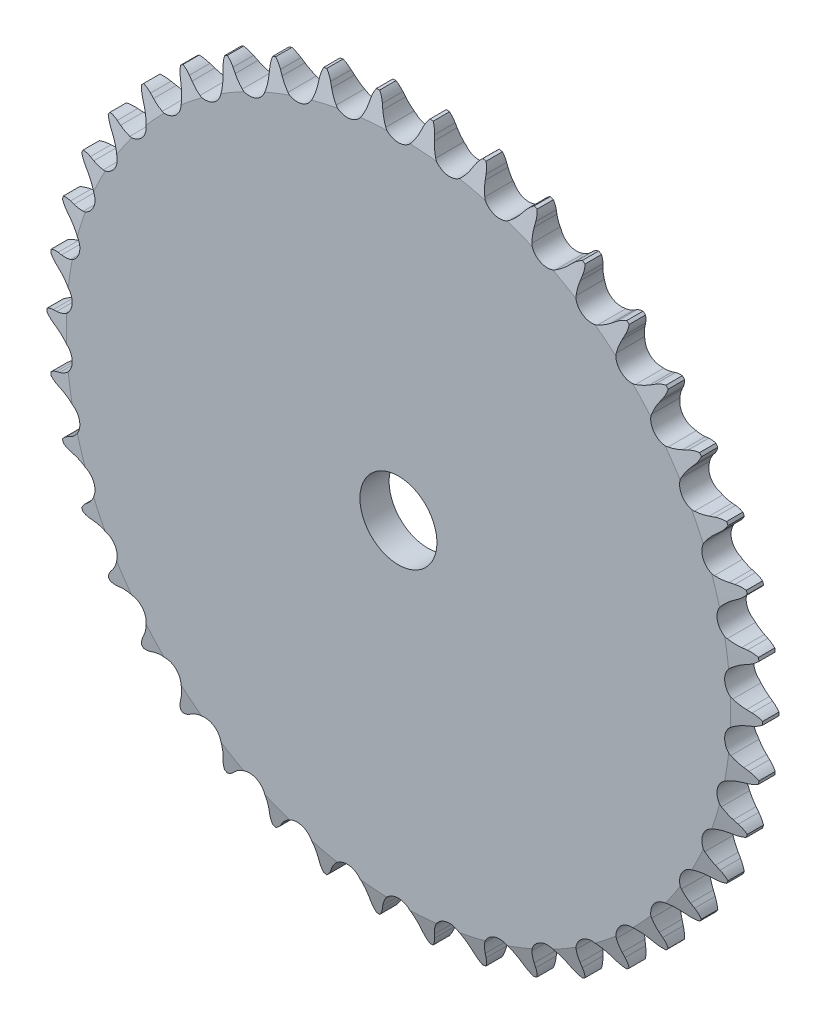
SolidWorks part; units mm, degrees
ref_plane "Front Plane" through (0, 0, 0) normal (0, 0, 1) x (1, 0, 0)
ref_plane "Top Plane" through (0, 0, 0) normal (0, 1, 0) x (1, 0, 0)
ref_plane "Right Plane" through (0, 0, 0) normal (1, 0, 0) x (0, 0, -1)
ref_axis "Axis1" through (0, 0, -88.99) along (0, 0, 1)
sketch "Sprocket-BaseSketch" plane through (0, 0, 0) normal (1, 0, 0) x (0, 0, -1)
  line L0 (3.6068, 0) -> (3.6068, 82.1949)
  line L1 (3.6068, 82.1949) -> (2.0193, 88.5449)
  line L2 (2.0193, 88.5449) -> (-2.0193, 88.5449)
  line L3 (-2.0193, 88.5449) -> (-3.6068, 82.1949)
  line L4 (-3.6068, 82.1949) -> (-3.6068, 0)
  line L5 (-3.6068, 0) -> (3.6068, 0)
  line L6 (14.4272, 0) -> (-4.5085, 0) construction
  dimension "Hub Surface" = 3.6068
  dimension "RightSide (1)" = 1.5875
  dimension "RightSide (2)" = 6.35
  dimension "OD" = 88.5449
  dimension "LeftSide (1)" = 1.5875
  dimension "LeftSide (2)" = 6.35
  dimension "Tooth Width" = 7.2136
revolve "40 (08A) ANSI (ISO) Chain Number, 6.691in P.D." add sketch "Sprocket-BaseSketch" angle 360 about L6
sketch "Tooth-Sketch" plane through (0, 0, 0) normal (0, 0, 1) x (1, 0, 0)
  line L0 (0, 0) -> (0, 113.2966) construction
  line L1 (4.649, 85.2343) -> (5.0352, 86.3092)
  line L2 (-4.649, 85.2343) -> (-5.0352, 86.3092)
  line L3 (0, 84.9725) -> (12.6645, 84.0234) construction
  line L4 (0, 84.9725) -> (-12.6645, 84.0234) construction
  arc A0 (-3.2347, 82.5851) -> (3.2347, 82.5851) centre (0, 84.9725) ccw
  arc A1 (3.2347, 82.5851) -> (4.649, 85.2343) centre (-5.101, 88.7372) ccw
  arc A2 (-3.2347, 82.5851) -> (-4.649, 85.2343) centre (5.101, 88.7372) cw
  arc A3 (5.0352, 86.3092) -> (11.0637, 90.5491) centre (11.0637, 84.1434) cw
  arc A4 (-5.0352, 86.3092) -> (-11.0637, 90.5491) centre (-11.0637, 84.1434) ccw
  arc A5 (11.0637, 90.5491) -> (-11.0637, 90.5491) centre (0, 0) ccw
extrude "Tooth-Cut, Number of teeth: 42" cut sketch "Tooth-Sketch" against normal through all and the other way through all
pattern_circular "Tooth Pattern, 42 / 42" count 42 every 8.571 about axis through (0, 0, -88.99) along (0, 0, 1) of "Tooth-Cut, Number of teeth: 42"
sketch "Sketch3" plane through (0, 0, 0) normal (1, 0, 0) x (0, 0, -1)
  line L0 (-21.3614, 0) -> (21.3614, 0) construction
  line L1 (3.6068, 0) -> (3.6068, 44.45)
  line L2 (3.6068, 44.45) -> (24.9682, 44.45)
  line L3 (24.9682, 44.45) -> (24.9682, 0)
  line L4 (24.9682, 0) -> (3.6068, 0)
  dimension "Hub Mounting" = 3.6068
  dimension "Hub OD" = 44.45
  dimension "Hub Width" = 21.3614
revolve "Hub-Revolve1" add sketch "Sketch3" angle 360 about L0
sketch "Sketch4" plane through (0, 0, -24.9682) normal (0, 0, -1) x (-1, 0, 0)
  circle A0 centre (0, 0) radius 9.525
  dimension "Bore Diameter " = 19.05
extrude "Cut-Extrude1" cut sketch "Sketch4" against normal through all
sketch "Sketch5" plane through (0, 0, 0) normal (1, 0, 0) x (0, 0, -1)
  line L0 (24.9682, 0) -> (-3.6068, 0) construction
  line L1 (24.9682, -44.45) -> (24.9682, 44.45) construction
  line L2 (-3.6068, 3.2885) -> (-3.6068, -3.2885) construction
ref_plane "Plane1" through (0, 0, 0) normal (-0.0747, 0.9972, 0) x (-0.9972, -0.0747, 0)
sketch "Sketch6" plane through (0, 0, -24.9682) normal (0, 0, -1) x (-1, 0, 0)
  line L0 (-1.6854, 9.3747) -> (-1.5074, 11.7493)
  line L1 (-1.5074, 11.7493) -> (3.2417, 11.3934)
  line L2 (3.2417, 11.3934) -> (3.0638, 9.0188)
  line L3 (3.0638, 9.0188) -> (-1.6854, 9.3747)
  line L4 (15.6723, -1.1745) -> (-15.6723, 1.1745) construction
  circle A0 centre (0, 0) radius 9.525 construction
  dimension "Keyway Wd " = 4.7625
  dimension "Keyway Dp " = 2.3813
extrude "Cut-Extrude2" [suppressed] cut sketch "Sketch6" against normal through all
sketch "Sketch7" [suppressed] plane through (-0.8672, 11.5713, 0) normal (0.0747, -0.9972, 0) x (0.9972, 0.0747, 0)
  line L0 (0, -24.9682) -> (0, -3.6068) construction
  line L1 (-44.45, -24.9682) -> (44.45, -24.9682) construction
  line L2 (-3.2885, -3.6068) -> (3.2885, -3.6068) construction
  line L3 (-2.3813, 3.6068) -> (-2.3813, -24.9682) construction
  circle A0 centre (0, -14.2875) radius 2.3813
extrude "Cut-Extrude3" [suppressed] cut sketch "Sketch7" against normal through all draft 1 draft outward yes
sketch "Sketch8" [suppressed] plane through (-0.8672, 11.5713, 0) normal (0.0747, -0.9972, 0) x (0.9972, 0.0747, 0)
  line L0 (-2.3813, -14.2875) -> (-2.9528, -14.2875) construction
  line L1 (-2.3813, 3.6068) -> (-2.3813, -24.9682) construction
  line L2 (-2.667, -14.2875) -> (-2.667, -24.9682) construction
  line L3 (-44.45, -24.9682) -> (44.45, -24.9682) construction
  circle A0 centre (0, -14.2875) radius 2.667
  arc A1 (-2.3813, -14.2875) -> (2.3813, -14.2875) centre (0, -14.2875) ccw construction
  spline S0 degree 3 poles (-2.1299, -16.3708) (-1.6696, -16.7322) (-1.5069, -16.8357) (-1.1637, -17.0098) (-0.9811, -17.081) (-0.6082, -17.1852) (-0.4187, -17.2186) (-0.0336, -17.2482) (0.163, -17.2439) (0.5457, -17.1976) (0.7337, -17.156) (1.103, -17.0351) (1.2812, -16.9564) (1.6164, -16.7676) (1.7759, -16.656) (2.0706, -16.4029) (2.2035, -16.2637) (2.4414, -15.9607) (2.547, -15.7949) (2.7214, -15.4504) (2.7912, -15.2711) (2.8955, -14.8983) (2.9295, -14.7052) (2.9589, -14.3213) (2.955, -14.1285) (2.9085, -13.7411) (2.8665, -13.5526) (2.747, -13.1867) (2.6683, -13.0074) (2.4785, -12.6698) (2.3682, -12.5122) (2.1173, -12.219) (1.9754, -12.0829) (1.6724, -11.8449) (1.5103, -11.7412) (1.1641, -11.5653) (0.9824, -11.4946) (0.6119, -11.3907) (0.4205, -11.3566) (0.0326, -11.3267) (-0.1599, -11.331) (-0.5425, -11.3768) (-0.7345, -11.4193) (-1.1017, -11.5394) (-1.2778, -11.6168) (-1.615, -11.8064) (-1.7757, -11.919) (-2.0678, -12.1695) (-2.2013, -12.3085) (-2.442, -12.6151) (-2.5458, -12.7781) (-2.7199, -13.1213) (-2.7911, -13.3036) (-2.8956, -13.6768) (-2.9291, -13.8663) (-2.9589, -14.2511) (-2.9548, -14.4478) (-2.9089, -14.8307) (-2.8676, -15.0187) (-2.7473, -15.3878) (-2.6688, -15.5665) (-2.3864, -16.0697) (-2.1299, -16.3708) (-1.6696, -16.7322) (-1.5069, -16.8357) knots -0.0625 -0.0625 0 0 0.03125 0.03125 0.0625 0.0625 0.09375 0.09375 0.125 0.125 0.15625 0.15625 0.1875 0.1875 0.21875 0.21875 0.25 0.25 0.28125 0.28125 0.3125 0.3125 0.34375 0.34375 0.375 0.375 0.40625 0.40625 0.4375 0.4375 0.46875 0.46875 0.5 0.5 0.53125 0.53125 0.5625 0.5625 0.59375 0.59375 0.625 0.625 0.65625 0.65625 0.6875 0.6875 0.71875 0.71875 0.75 0.75 0.78125 0.78125 0.8125 0.8125 0.84375 0.84375 0.875 0.875 0.90625 0.90625 0.9375 0.9375 1 1 1.03125 1.03125 1.0625 only from (-1.8231, -16.6117) to (-1.8231, -16.6117) construction
extrude "Extrude1" [suppressed] add sketch "Sketch8" against normal up to surface (32.7661 mm away)
sketch "Sketch9" [suppressed] plane through (-0.8672, 11.5713, 0) normal (0.0747, -0.9972, 0) x (0.9972, 0.0747, 0)
  line L0 (0, -14.2875) -> (2.667, -14.2875) construction
  line L1 (1.3335, -14.2875) -> (1.3335, -16.5972) construction
  line L3 (0, -15.8273) -> (1.3335, -15.0574)
  line L4 (1.3335, -15.0574) -> (1.3335, -13.5176)
  line L5 (1.3335, -13.5176) -> (0, -12.7477)
  line L6 (0, -12.7477) -> (-1.3335, -13.5176)
  line L7 (-1.3335, -13.5176) -> (-1.3335, -15.0574)
  line L8 (-1.3335, -15.0574) -> (0, -15.8273)
  circle A0 centre (0, -14.2875) radius 2.667 construction
  circle A1 centre (0, -14.2875) radius 1.3335 construction
extrude "Cut-Extrude4" [suppressed] cut sketch "Sketch9" against normal through all from offset 2.54 offset against normal yes
pattern_circular "CirPattern1" [suppressed] count 2 over 90 about axis through (0, 0, 21.3614) along (0, 0, -1) of bodies 109
sketch "Sketch10" plane through (0, 0, -24.9682) normal (0, 0, -1) x (-1, 0, 0)
  line L0 (-88.2973, 6.617) -> (88.2973, -6.617)
  line L1 (-12.6645, -84.0234) -> (0, -84.9725)
  line L2 (15.6723, -1.1745) -> (-15.6723, 1.1745) construction
  line L3 (-88.6935, 1.3295) -> (87.901, -11.9044)
  line L4 (-12.2683, -78.736) -> (0.3962, -79.685)
  circle A0 centre (0, 0) radius 88.5449
  circle A1 centre (0, 0) radius 9.525
  circle A2 centre (0, 0) radius 9.525 construction
  arc A3 (79.9513, 38.0524) -> (79.5994, 38.7831) centre (0, 0) ccw construction
  dimension "D1" = 5.3022
  dimension "D2" = 5.3022
sketch "Sketch11" plane through (0, 0, 0) normal (0, 1, 0) x (1, 0, 0)
  line L0 (44.45, 3.6068) -> (-44.45, 3.6068) construction
  line L1 (-101.6, 85.9283) -> (101.6, 85.9283)
  line L2 (-101.6, 85.9283) -> (-101.6, 3.6068)
  line L3 (-101.6, 3.6068) -> (101.6, 3.6068)
  line L4 (101.6, 85.9283) -> (101.6, 3.6068)
  line L5 (-101.6, 85.9283) -> (101.6, 3.6068) construction
  line L6 (-101.6, 3.6068) -> (101.6, 85.9283) construction
  line L7 (44.45, 3.6068) -> (-44.45, 3.6068)
  line L8 (0, -15.7163) -> (0, 15.7163) construction
  point P0 (0, 44.7676)
  dimension "D1" = 203.2
extrude "Cut-Extrude5" cut sketch "Sketch11" against normal mid plane 203.2 contours L4 L1 L2 L3 region at (0, 0, -44.7676)
sketch "Sketch12" plane through (0, 0, -3.6068) normal (0, 0, -1) x (-1, 0, 0)
  circle A0 centre (0, 0) radius 40.2167
  dimension "D1" = 80.4333
extrude "Cut-Extrude6" [suppressed] cut sketch "Sketch12"
equation "\"D1@Sketch10\" = \"D2@Sketch10\""
